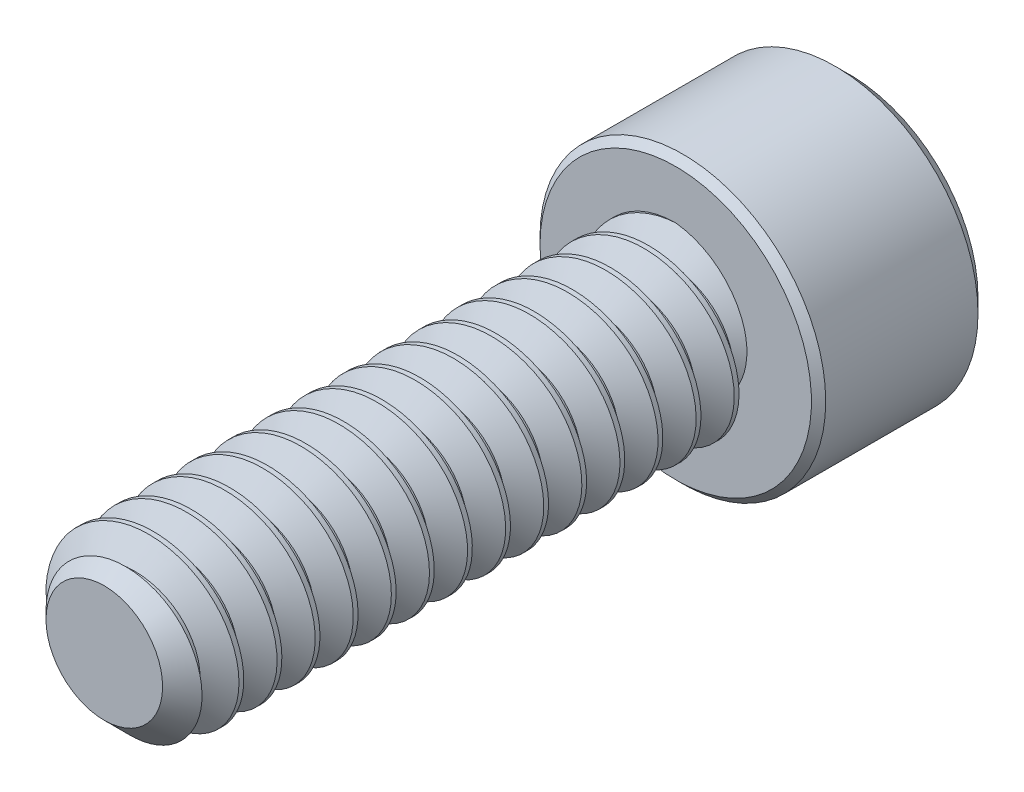
SolidWorks part; units mm, degrees
ref_plane "Front Plane" through (0, 0, 0) normal (0, 0, 1) x (1, 0, 0)
ref_plane "Top Plane" through (0, 0, 0) normal (0, 1, 0) x (1, 0, 0)
ref_plane "Right Plane" through (0, 0, 0) normal (1, 0, 0) x (0, 0, -1)
sketch "Sketch0" plane through (0, 0, 0) normal (1, 0, 0) x (0, 0, -1)
  line L0 (0, 0) -> (15.875, 0) construction
  point P2 (20.701, 0)
  point P4 (0, 0)
  dimension "D1" = 15.875
  dimension "D2" = 4.826
  dimension "Min Thread" = 0
sketch "Sketch1" plane through (0, 0, 0) normal (0, 0, 1) x (1, 0, 0)
  circle A0 centre (0, 0) radius 2.413
  dimension "OD" = 4.826
extrude "Extrude1" add sketch "Sketch1" against normal blind 15.875
sketch "Sketch2" plane through (0, 0, 0) normal (0, 0, 1) x (1, 0, 0)
  circle A0 centre (0, 0) radius 2.413 construction
  circle A1 centre (0, 0) radius 2.413
curve "Helix/Spiral1" pitch 1.0583 height 16.9333 turns 16 parameters "pitch"=1.0583
chamfer "Chamfer3" distance 0.7937 angle 45 1 edges at (2.413, 0, 0)
sketch "Sketch3" plane through (0, 0, 0) normal (1, 0, 0) x (0, 0, -1)
  line L0 (-0.926, 2.413) -> (-0.5292, 1.7256)
  line L1 (-0.5292, 1.7256) -> (-0.3969, 1.7256)
  line L2 (-0.3969, 1.7256) -> (0, 2.413)
  line L3 (-0.926, 2.413) -> (0, 2.413)
  line L4 (-0.463, 2.413) -> (-0.463, 1.7256) construction
  line L5 (-0.7276, 2.0693) -> (-0.1984, 2.0693) construction
  line L6 (0, 2.413) -> (0, -2.413) construction
  dimension "D1" = 0.1323
  dimension "D2" = 0.5292
  dimension "D3" = 60
sweep "Cut-Sweep1" cut profiles "Sketch3" path "Helix/Spiral1"
sketch "Sketch5" plane through (0, 0, 0) normal (1, 0, 0) x (0, 0, -1)
  line L0 (15.875, -1.7471) -> (15.875, 1.7217) construction
  line L1 (15.875, 2.413) -> (0, 2.413)
  line L2 (15.875, 2.413) -> (15.875, 0)
  line L3 (15.875, 0) -> (-0.8783, 0)
  line L4 (0, 0) -> (15.875, 0) construction
  line L5 (0, 2.413) -> (-0.8783, 0)
  line L6 (0, 0) -> (18.415, 0) construction
  dimension "D1" = 70
  dimension "D3" = 2.54
revolve "partially thread" [suppressed] add sketch "Sketch5" angle 360 about L6
sketch "Sketch6" plane through (0, 0, -15.875) normal (0, 0, -1) x (-1, 0, 0)
  circle A0 centre (0, 0) radius 3.9688
  dimension "head dia" = 7.9375
extrude "Extrude2" add sketch "Sketch6" along normal blind 4.826
sketch "Sketch7" plane through (0, 0, -20.701) normal (0, 0, -1) x (-1, 0, 0)
  line L1 (0, 2.2914) -> (-1.9844, 1.1457)
  line L2 (-1.9844, 1.1457) -> (-1.9844, -1.1457)
  line L3 (-1.9844, -1.1457) -> (0, -2.2914)
  line L4 (0, -2.2914) -> (1.9844, -1.1457)
  line L5 (1.9844, -1.1457) -> (1.9844, 1.1457)
  line L6 (1.9844, 1.1457) -> (0, 2.2914)
  circle A0 centre (0, 0) radius 1.9844 construction
  dimension "hex dia" = 3.9688
extrude "Cut-Extrude1" cut sketch "Sketch7" against normal blind 2.9766
sketch "Sketch8" plane through (0, 0, -20.701) normal (0, 0, -1) x (-1, 0, 0)
  circle A0 centre (0, 0) radius 2.2914
extrude "Cut-Extrude2" cut sketch "Sketch8" against normal through all draft 45
chamfer "Chamfer1" distance 0.3969 angle 45 1 edges at (-3.9688, 0, -20.701)
chamfer "Chamfer2" distance 0.1984 angle 45 1 edges at (-3.9688, 0, -15.875)
sketch "Sketch9" plane through (0, 0, 0) normal (1, 0, 0) x (0, 0, -1)
  line L0 (0, 2.413) -> (0, -2.413) construction
  line L1 (2.6458, 2.413) -> (2.6458, -2.413) construction
  line L2 (20.701, 3.9688) -> (20.701, -3.9688) construction
  line L3 (15.875, 3.9688) -> (15.875, -3.9688) construction
  line L4 (15.875, 3.7703) -> (15.875, -3.7703) construction
  line L5 (20.701, -3.5719) -> (20.701, 3.5719) construction
  line L6 (15.875, -3.9688) -> (15.875, 3.9688) construction
  line L7 (0, 1.6193) -> (0, -1.6193) construction
  line L8 (-0.926, 2.413) -> (0, 2.413) construction
  line L9 (2.6458, 0) -> (0, 0) construction
  dimension "D1" = 2.6458
equation "\"D3@Helix/Spiral1\" = \"screw length@Extrude1\"+\"pitch@Helix/Spiral1\""
equation "\"D1@Sketch3\" = \"pitch@Helix/Spiral1\"*.125"
equation "\"D2@Sketch3\" = \"pitch@Helix/Spiral1\"*.5"
equation "\"D1@Cut-Extrude1\" = \"hex dia@Sketch7\"*.75"
equation "\"D1@Chamfer1\" = \"head dia@Sketch6\"*.05"
equation "\"D1@Sketch9\" = \"pitch@Helix/Spiral1\"*2.50"
equation "\"D1@Chamfer2\" = \"D1@Chamfer1\"/2"
equation "\"D1@Chamfer3\" = \"pitch@Helix/Spiral1\"*.750"
equation "\"D1@Sketch0\" = \"screw length@Extrude1\""
equation "\"D2@Sketch0\" = \"head depth@Extrude2\""
